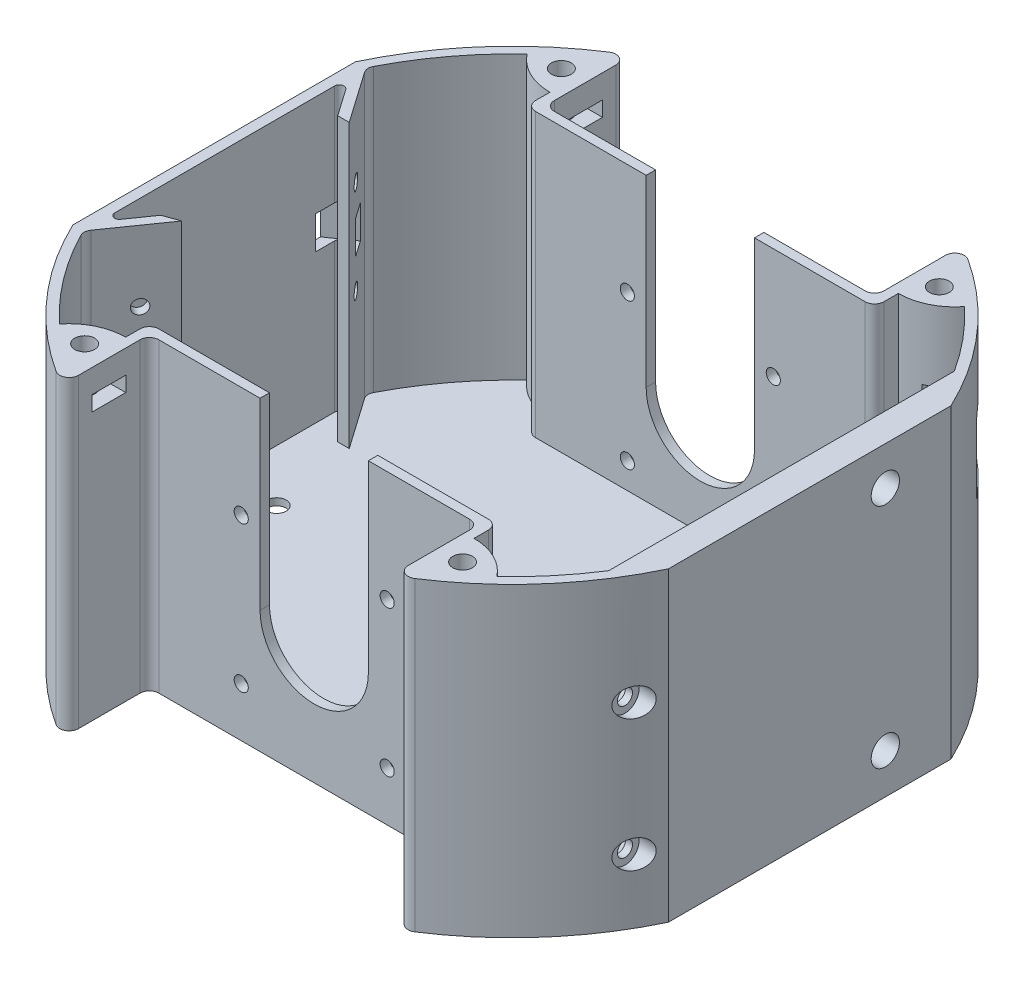
SolidWorks part; units mm, degrees
ref_plane "Plan de face" through (0, 0, 0) normal (0, 0, 1) x (1, 0, 0)
ref_plane "Plan de dessus" through (0, 0, 0) normal (0, 1, 0) x (1, 0, 0)
ref_plane "Plan de droite" through (0, 0, 0) normal (1, 0, 0) x (0, 0, -1)
sketch "Esquisse1" plane through (0, 0, 0) normal (0, 1, 0) x (1, 0, 0)
  line L0 (0, 7.0991) -> (0, -9.5713) construction
  line L1 (-20.3786, 0) -> (23.686, 0) construction
  line L2 (35, 42) -> (-35, 42)
  line L7 (-63.2456, -30) -> (-63.2456, 30)
  line L8 (-35, 42) -> (-35, 60.6218)
  line L9 (-21, 0) -> (-21, 42) construction
  line L12 (-35, -42) -> (-35, -60.6218)
  line L13 (35, -42) -> (-35, -42)
  line L15 (35, -42) -> (35, -60.6218)
  line L16 (63.2456, -30) -> (63.2456, 30)
  line L17 (35, 42) -> (35, 60.6218)
  circle A0 centre (0, 0) radius 70 construction
  arc A1 (-63.2456, 30) -> (-35, 60.6218) centre (0, 0) cw
  arc A2 (-63.2456, -30) -> (-35, -60.6218) centre (0, 0) ccw
  arc A3 (63.2456, -30) -> (35, -60.6218) centre (0, 0) cw
  arc A4 (63.2456, 30) -> (35, 60.6218) centre (0, 0) ccw
  circle A5 centre (-50, 0) radius 2.05
  circle A6 centre (50, 0) radius 2.05
  point P16 (-63.2456, 0)
  point P20 (0, -42)
  point P25 (0, 42)
  dimension "D1" = 140
  dimension "D2" = 42
  dimension "D6" = 4.1
  dimension "D3" = 35
  dimension "D4" = 30
  dimension "D5" = 21
  dimension "D7" = 50
extrude "Boss.-Extru.1" add sketch "Esquisse1" along normal blind 5
sketch "Esquisse3" plane through (0, 5, 0) normal (0, 1, 0) x (1, 0, 0)
  line L0 (-100.0452, 0) -> (128.6597, 0) construction
  line L1 (0, 78.0074) -> (0, -84.0534) construction
  line L2 (-61.0246, -30) -> (-61.0246, 30)
  line L3 (37, 40) -> (-37, 40)
  line L4 (-37, 40) -> (-37, 57.0526)
  line L5 (-63.2456, 30) -> (-61.0246, 30) construction
  line L6 (-37, -40) -> (-37, -57.0526)
  line L7 (37, -40) -> (-37, -40)
  line L8 (-35, 42) -> (-35, 60.6218)
  line L9 (-63.2456, 30) -> (-63.2456, -30)
  line L10 (-35, -60.6218) -> (-35, -42)
  line L11 (-35, -42) -> (35, -42)
  line L12 (35, -42) -> (35, -60.6218)
  line L13 (63.2456, -30) -> (63.2456, 30)
  line L14 (35, 60.6218) -> (35, 42)
  line L15 (35, 42) -> (-35, 42)
  line L16 (-35, 42) -> (-35, 60.6218)
  line L17 (-63.2456, 30) -> (-63.2456, -30)
  line L18 (-35, -60.6218) -> (-35, -42)
  line L19 (-35, -42) -> (35, -42)
  line L20 (35, -42) -> (35, -60.6218)
  line L21 (63.2456, -30) -> (63.2456, 30)
  line L22 (35, 60.6218) -> (35, 42)
  line L23 (35, 42) -> (-35, 42)
  line L24 (37, -40) -> (37, -57.0526)
  line L25 (61.0246, -30) -> (61.0246, 30)
  line L26 (37, 40) -> (37, 57.0526)
  line L27 (-61.0246, 30) -> (-52.4209, 17.7127)
  line L28 (-52.4209, 17.7127) -> (-54.0592, 16.5656)
  line L29 (-54.0592, 16.5656) -> (-61.0246, 26.5131)
  line L30 (-56.7228, 23.8564) -> (-177.37, -60.6218) construction
  line L31 (-52.4209, -17.7127) -> (-54.0592, -16.5656)
  line L32 (-61.0246, -30) -> (-52.4209, -17.7127)
  line L33 (-54.0592, -16.5656) -> (-61.0246, -26.5131)
  line L34 (-56.7228, -23.8564) -> (-177.37, 60.6218) construction
  line L35 (57.2456, 36.7008) -> (57.2456, -36.7008)
  line L36 (51.2707, 60.6218) -> (-111.4939, 60.6218) construction
  line L37 (51.2707, -60.6218) -> (-111.4939, -60.6218) construction
  line L38 (-63.2456, 45.1535) -> (-63.2456, -75.8674) construction
  line L39 (-97.9861, 0) -> (-97.9861, -104.005) construction
  circle A0 centre (0, 0) radius 68 construction
  arc A1 (-37, 57.0526) -> (-61.0246, 30) centre (0, 0) ccw
  arc A2 (-46.4527, 49.6603) -> (-37, 45.0526) centre (-37, 57.0526) ccw
  arc A3 (-37, -57.0526) -> (-61.0246, -30) centre (0, 0) cw
  arc A4 (-35, 60.6218) -> (-63.2456, 30) centre (0, 0) ccw
  arc A5 (-63.2456, -30) -> (-35, -60.6218) centre (0, 0) ccw
  arc A6 (35, -60.6218) -> (63.2456, -30) centre (0, 0) ccw
  arc A7 (63.2456, 30) -> (35, 60.6218) centre (0, 0) ccw
  arc A8 (-35, 60.6218) -> (-63.2456, 30) centre (0, 0) ccw
  arc A9 (-63.2456, -30) -> (-35, -60.6218) centre (0, 0) ccw
  arc A10 (35, -60.6218) -> (63.2456, -30) centre (0, 0) ccw
  arc A11 (63.2456, 30) -> (35, 60.6218) centre (0, 0) ccw
  arc A12 (-46.4527, -49.6603) -> (-37, -45.0526) centre (-37, -57.0526) cw
  arc A13 (37, -57.0526) -> (61.0246, -30) centre (0, 0) ccw
  arc A14 (46.4527, -49.6603) -> (37, -45.0526) centre (37, -57.0526) ccw
  arc A15 (37, 57.0526) -> (61.0246, 30) centre (0, 0) cw
  arc A16 (46.4527, 49.6603) -> (37, 45.0526) centre (37, 57.0526) cw
  circle A17 centre (-134.3793, 0) radius 25 construction
  point P29 (-61.0246, 0)
  point P40 (0, -40)
  point P45 (0, 40)
  point P67 (-149.5717, 0)
  point P68 (0, 0)
  line M27 (-35, 42) -> (-35, 60.6218)
  arc M28 (-35, 60.6218) -> (-63.2456, 30) centre (0, 0) ccw
  line M29 (-63.2456, 30) -> (-63.2456, -30)
  arc M30 (-63.2456, -30) -> (-35, -60.6218) centre (0, 0) ccw
  line M31 (-35, -60.6218) -> (-35, -42)
  line M32 (-35, -42) -> (35, -42)
  line M33 (35, -42) -> (35, -60.6218)
  arc M34 (35, -60.6218) -> (63.2456, -30) centre (0, 0) ccw
  line M35 (63.2456, -30) -> (63.2456, 30)
  arc M36 (63.2456, 30) -> (35, 60.6218) centre (0, 0) ccw
  line M37 (35, 60.6218) -> (35, 42)
  line M38 (35, 42) -> (-35, 42)
  dimension "D2" = 136
  dimension "D3" = 2
  dimension "D5" = 12
  dimension "D13" = 50
  dimension "D4" = 2
  dimension "D6" = 2
  dimension "D7" = 15
  dimension "D8" = 35
  dimension "D9" = 6
  dimension "D11" = 114.1245
  dimension "D12" = 34.7406
  dimension "D14" = 71.1338
  dimension "D1" = 0
extrude "Boss.-Extru.2" add sketch "Esquisse3" along normal blind 60 contours L26 A15 L25 A13 L24 L7 L6 A3 L2 A1 L4 L3 M38 M27 M28 M29 M30 M31 M32 M33 M34 M35 M36 M37 | L29 L28 L27 L2 | A12 A3 L6 | A16 A15 L26 | A13 A14 L24 | L31 L33 L2 L32 | A15 L35 A13 L25 | A1 A2 L4
sketch "Esquisse4" plane through (0, 0, -40) normal (0, 0, 1) x (1, 0, 0)
  line L0 (0, -2.1196) -> (0, 67.1313) construction
  line L1 (0, 104) -> (0, 26) construction
  line L2 (11.5, 104) -> (11.5, 26)
  line L3 (-11.5, 104) -> (-11.5, 26)
  line L4 (-37, 5) -> (37, 5)
  line L5 (37, 5) -> (37, 65)
  line L6 (37, 65) -> (-37, 65)
  line L7 (-37, 65) -> (-37, 5)
  line L8 (-37, 5) -> (37, 5)
  line L9 (37, 5) -> (37, 65)
  line L10 (37, 65) -> (-37, 65)
  line L11 (-37, 65) -> (-37, 5)
  line L12 (-35, 0) -> (35, 0) construction
  line L13 (-35, 0) -> (35, 0)
  line L14 (31.9264, 26) -> (-22.6349, 26) construction
  arc A0 (11.5, 104) -> (-11.5, 104) centre (0, 104) ccw
  arc A1 (-11.5, 26) -> (11.5, 26) centre (0, 26) ccw
  circle A2 centre (-15.5, 41.5) radius 1.5
  circle A3 centre (-15.5, 10.5) radius 1.5
  circle A4 centre (15.5, 10.5) radius 1.5
  circle A5 centre (15.5, 41.5) radius 1.5
  point P9 (0, 65)
  line M14 (37, 65) -> (-37, 65)
  dimension "D3" = 15.5
  dimension "D5" = 3
  dimension "D2" = 23
  dimension "D4" = 15.5
  dimension "D6" = 26
  dimension "D1" = 0
extrude "Enlèv. mat.-Extru.1" cut sketch "Esquisse4" against normal through all both and the other way through all contours L3 A1 L2 M14 | A3 | A2 | A5 | A4
sketch "Esquisse7" plane through (0, 65, 0) normal (0, 1, 0) x (1, 0, 0)
  line L0 (-35, -60.6218) -> (-49.7114, -60.6218) construction
  line L1 (-46.4527, -49.6603) -> (-37, -45.0526) construction
  line L2 (-41.7264, -47.3565) -> (-37, -57.0526) construction
  line L12 (-11.5, 40) -> (-11.5, 42)
  line L13 (-11.5, 42) -> (-35, 42)
  line L14 (-35, 42) -> (-35, 60.6218)
  line L15 (-63.2456, 30) -> (-63.2456, -30)
  line L16 (-35, -60.6218) -> (-35, -42)
  line L17 (-35, -42) -> (-11.5, -42)
  line L24 (-11.5, 40) -> (-11.5, 42)
  line L25 (-11.5, 42) -> (-35, 42)
  line L26 (-35, 42) -> (-35, 60.6218)
  line L27 (-63.2456, 30) -> (-63.2456, -30)
  line L28 (-35, -60.6218) -> (-35, -42)
  line L29 (-35, -42) -> (-11.5, -42)
  line L39 (-11.5, -42) -> (-11.5, -40)
  line L41 (-11.5, -42) -> (-11.5, -40)
  line L43 (-11.5, -40) -> (-37, -40)
  line L45 (-11.5, -40) -> (-37, -40)
  line L47 (-37, -40) -> (-37, -45.0526)
  line L49 (-37, -40) -> (-37, -45.0526)
  line L51 (-61.0246, -26.5131) -> (-61.0246, 26.5131)
  line L53 (-61.0246, -26.5131) -> (-61.0246, 26.5131)
  line L55 (-37, 45.0526) -> (-37, 40)
  line L57 (-37, 45.0526) -> (-37, 40)
  line L59 (-37, 40) -> (-11.5, 40)
  line L61 (-37, 40) -> (-11.5, 40)
  line L63 (-61.0246, -30) -> (-52.4209, -17.7127)
  line L64 (-61.0246, -30) -> (-52.4209, -17.7127)
  line L65 (-52.4209, -17.7127) -> (-54.0592, -16.5656)
  line L66 (-52.4209, -17.7127) -> (-54.0592, -16.5656)
  line L67 (-54.0592, -16.5656) -> (-61.0246, -26.5131)
  line L68 (-54.0592, -16.5656) -> (-61.0246, -26.5131)
  line L69 (-61.0246, 26.5131) -> (-54.0592, 16.5656)
  line L70 (-61.0246, 26.5131) -> (-54.0592, 16.5656)
  line L71 (-54.0592, 16.5656) -> (-52.4209, 17.7127)
  line L72 (-54.0592, 16.5656) -> (-52.4209, 17.7127)
  line L73 (-52.4209, 17.7127) -> (-61.0246, 30)
  line L74 (-52.4209, 17.7127) -> (-61.0246, 30)
  circle A1 centre (-40.1347, -50.6218) radius 2.1
  arc A6 (-35, 60.6218) -> (-63.2456, 30) centre (0, 0) ccw
  arc A7 (-63.2456, -30) -> (-35, -60.6218) centre (0, 0) ccw
  arc A9 (-37, -45.0526) -> (-46.4527, -49.6603) centre (-37, -57.0526) ccw
  arc A10 (-37, -45.0526) -> (-46.4527, -49.6603) centre (-37, -57.0526) ccw
  arc A12 (-35, 60.6218) -> (-63.2456, 30) centre (0, 0) ccw
  arc A13 (-63.2456, -30) -> (-35, -60.6218) centre (0, 0) ccw
  arc A18 (-61.0246, -30) -> (-46.4527, -49.6603) centre (0, 0) ccw
  arc A20 (-61.0246, -30) -> (-46.4527, -49.6603) centre (0, 0) ccw
  arc A22 (-46.4527, 49.6603) -> (-61.0246, 30) centre (0, 0) ccw
  arc A24 (-46.4527, 49.6603) -> (-61.0246, 30) centre (0, 0) ccw
  arc A26 (-46.4527, 49.6603) -> (-37, 45.0526) centre (-37, 57.0526) ccw
  arc A27 (-46.4527, 49.6603) -> (-37, 45.0526) centre (-37, 57.0526) ccw
  dimension "D2" = 4.2
  dimension "D3" = 10
  dimension "D4" = 5.1347
  dimension "D1" = 0
extrude "Enlèv. mat.-Extru.2" cut sketch "Esquisse7" against normal blind 13 contours A1
sketch "Esquisse8" plane through (-35, 0, 0) normal (1, 0, 0) x (0, 0, -1)
  line L1 (-47.0218, 56.8) -> (-54.2218, 56.8)
  line L2 (-47.0218, 56.8) -> (-47.0218, 60)
  line L3 (-47.0218, 60) -> (-54.2218, 60)
  line L4 (-60.6218, 0) -> (-42, 0)
  line L5 (-42, 0) -> (-42, 65)
  line L6 (-42, 65) -> (-60.6218, 65)
  line L7 (-60.6218, 65) -> (-60.6218, 0)
  line L8 (-60.6218, 0) -> (-42, 0)
  line L9 (-42, 0) -> (-42, 65)
  line L10 (-42, 65) -> (-60.6218, 65)
  line L11 (-60.6218, 65) -> (-60.6218, 0)
  line L12 (-54.2218, 56.8) -> (-54.2218, 60)
  line L13 (-47.0218, 56.8) -> (-54.2218, 60) construction
  line L14 (-47.0218, 60) -> (-54.2218, 56.8) construction
  point P2 (-50.6218, 58.4)
  dimension "D2" = 10
  dimension "D3" = 7.2
  dimension "D4" = 3.2
  dimension "D5" = 5
  dimension "D1" = 0
extrude "Enlèv. mat.-Extru.3" cut sketch "Esquisse8" against normal blind 5 contours L2 L1 L12 L3
sketch "Esquisse10" plane through (0, 65, 0) normal (0, 1, 0) x (1, 0, 0)
  line L0 (-40.1347, -50.6218) -> (-35, -50.6218) construction
  line L1 (-35.9778, -50.6218) -> (-38.0562, -47.0218)
  line L2 (-38.0562, -47.0218) -> (-42.2131, -47.0218)
  line L3 (-42.2131, -47.0218) -> (-44.2916, -50.6218)
  line L4 (-44.2916, -50.6218) -> (-42.2131, -54.2218)
  line L5 (-42.2131, -54.2218) -> (-38.0562, -54.2218)
  line L6 (-38.0562, -54.2218) -> (-35.9778, -50.6218)
  line L7 (-35, -60.6218) -> (-35, -42) construction
  circle A0 centre (-40.1347, -50.6218) radius 2.1 construction
  circle A1 centre (-40.1347, -50.6218) radius 2.1
  circle A2 centre (-40.1347, -50.6218) radius 3.6 construction
  dimension "D1" = 7.2
extrude "Enlèv. mat.-Extru.4" cut sketch "Esquisse10" against normal blind 3.2 from offset 5
mirror "Symétrie1" about plane through (0, 0, 0) normal (1, 0, 0) of "Enlèv. mat.-Extru.4", "Enlèv. mat.-Extru.3", "Enlèv. mat.-Extru.2"
mirror "Symétrie2" about plane through (0, 0, 0) normal (0, 0, 1) of "Symétrie1", "Enlèv. mat.-Extru.4", "Enlèv. mat.-Extru.3", "Enlèv. mat.-Extru.2"
fillet "Congé1" radius 2 14 edges at (37, 35, -40) (-35, 32.5, -42) (35, 32.5, -42) (-37, 35, -40) (-35, 32.5, 60.6218) (-35, 32.5, -60.6218) (35, 32.5, -60.6218) (-37, 35, 40) (37, 35, 40) (35, 32.5, 42) (-35, 32.5, 42) (35, 32.5, 60.6218) (-61.0246, 35, -30) (-61.0246, 35, 30)
fillet "Congé2" radius 1 2 edges at (-61.0246, 35, -26.5131) (-61.0246, 35, 26.5131)
sketch "Esquisse13" plane through (0, 0, 0) normal (0, -1, 0) x (1, 0, 0)
  circle A0 centre (-50, 0) radius 2.05 construction
  circle A1 centre (-50, 0) radius 2.05
  circle A2 centre (50, 0) radius 2.05 construction
  circle A3 centre (50, 0) radius 2.05
  circle A4 centre (-50, 0) radius 12.75
  circle A5 centre (50, 0) radius 12.75
  dimension "D1" = 25.5
extrude "Enlèv. mat.-Extru.5" cut sketch "Esquisse13" against normal blind 3.5
sketch "Esquisse14" plane through (-26.8527, 0, -18.8025) normal (0.8192, 0, 0.5736) x (0.5736, 0, -0.8192)
  line L0 (-50.9268, 65) -> (-50.9268, 5) construction
  line L1 (-44.5768, 40) -> (-58.3826, 40) construction
  line L2 (-45.5768, 65) -> (-45.5768, 5) construction
  line L4 (-44.5768, 65) -> (-58.3826, 65)
  line L5 (-58.3826, 65) -> (-58.3826, 5)
  line L6 (-58.3826, 5) -> (-44.5768, 5)
  line L7 (-44.5768, 5) -> (-44.5768, 65)
  line L8 (-44.5768, 65) -> (-58.3826, 65)
  line L9 (-58.3826, 65) -> (-58.3826, 5)
  line L10 (-58.3826, 5) -> (-44.5768, 5)
  line L11 (-44.5768, 5) -> (-44.5768, 65)
  line L15 (-54.7768, 43.5) -> (-50.7768, 43.5)
  line L16 (-54.7768, 43.5) -> (-54.7768, 36.5)
  line L17 (-54.7768, 36.5) -> (-50.7768, 36.5)
  line L18 (-50.7768, 43.5) -> (-50.7768, 36.5)
  line L19 (-54.7768, 43.5) -> (-50.7768, 36.5) construction
  line L20 (-54.7768, 36.5) -> (-50.7768, 43.5) construction
  circle A0 centre (-50.9268, 50) radius 1.5
  circle A2 centre (-50.9268, 30) radius 1.5
  point P12 (-50.9268, 40)
  point P13 (-52.7768, 40)
  dimension "D2" = 20
  dimension "D3" = 3
  dimension "D4" = 4
  dimension "D5" = 7
  dimension "D6" = 1
  dimension "D7" = 35
  dimension "D8" = 9.2
  dimension "D9" = 5.35
  dimension "D1" = 0
extrude "Enlèv. mat.-Extru.6" cut sketch "Esquisse14" against normal blind 5 contours L17 L18 L15 L16 | A0 | A2
sketch "Esquisse16" plane through (-26.8527, 0, -18.8025) normal (0.8192, 0, 0.5736) x (0.5736, 0, -0.8192)
  line L0 (-50.7768, 43.5) -> (-50.7768, 36.5) construction
  line L1 (-54.7768, 43.5) -> (-50.7768, 43.5) construction
  line L2 (-54.7768, 43.5) -> (-54.7768, 36.5) construction
  line L3 (-54.7768, 36.5) -> (-50.7768, 36.5) construction
  line L4 (-50.7768, 43.5) -> (-50.7768, 36.5)
  line L5 (-54.7768, 43.5) -> (-50.7768, 43.5)
  line L6 (-54.7768, 43.5) -> (-54.7768, 36.5)
  line L7 (-54.7768, 36.5) -> (-50.7768, 36.5)
extrude "Enlèv. mat.-Extru.8" cut sketch "Esquisse16" against normal through all
mirror "Symétrie3" about plane through (0, 0, 0) normal (0, 0, 1) of "Enlèv. mat.-Extru.8", "Enlèv. mat.-Extru.6"
sketch "Esquisse18" plane through (57.2456, 0, 0) normal (-1, 0, 0) x (0, 0, 1)
  line L0 (-16.05, 59.34) -> (-16.05, 6) construction
  line L1 (37.29, 6) -> (-31.29, 6) construction
  line L4 (-36.7008, 5) -> (36.7008, 5)
  line L5 (36.7008, 5) -> (36.7008, 65)
  line L6 (36.7008, 65) -> (-36.7008, 65)
  line L7 (-36.7008, 65) -> (-36.7008, 5)
  line L8 (-36.7008, 5) -> (36.7008, 5) construction
  line L9 (36.7008, 5) -> (36.7008, 65) construction
  line L10 (36.7008, 65) -> (-36.7008, 65) construction
  line L11 (-36.7008, 65) -> (-36.7008, 5) construction
  line L14 (37.29, 6) -> (37.29, 59.34) construction
  line L16 (-30, 0) -> (30, 0) construction
  line L17 (37.29, 59.34) -> (-31.29, 59.34) construction
  line L18 (-31.29, 6) -> (-31.29, 59.34) construction
  line L19 (37.29, 6) -> (-31.29, 59.34) construction
  line L20 (37.29, 59.34) -> (-31.29, 6) construction
  line L21 (34.75, 59.34) -> (34.75, 6) construction
  circle A4 centre (-16.05, 56.8) radius 1.6
  circle A5 centre (-16.05, 8.54) radius 1.6
  circle A6 centre (34.75, 41.56) radius 1.6
  circle A7 centre (34.75, 13.62) radius 1.6
  point P4 (3, 32.67)
  dimension "D2" = 3.2
  dimension "D3" = 2.54
  dimension "D4" = 50.8
  dimension "D5" = 53.34
  dimension "D6" = 68.58
  dimension "D7" = 15.24
  dimension "D8" = 66.04
  dimension "D9" = 17.78
  dimension "D10" = 45.72
  dimension "D11" = 6
  dimension "D12" = 3
  dimension "D1" = 0
extrude "Enlèv. mat.-Extru.10" cut sketch "Esquisse18" against normal blind 10 and the other way blind 2.5
sketch "Esquisse19" plane through (63.2456, 0, 0) normal (1, 0, 0) x (0, 0, -1)
  circle A0 centre (16.05, 8.54) radius 1.6 construction
  circle A3 centre (16.05, 56.8) radius 1.6 construction
  circle A4 centre (16.05, 8.54) radius 1.6
  circle A7 centre (16.05, 56.8) radius 1.6
  circle A8 centre (-34.75, 41.56) radius 3
  circle A9 centre (16.05, 56.8) radius 3
  circle A10 centre (-34.75, 13.62) radius 3
  circle A11 centre (16.05, 8.54) radius 3
  circle A12 centre (-34.75, 13.62) radius 1.6 construction
  circle A13 centre (-34.75, 41.56) radius 1.6 construction
  circle A14 centre (-34.75, 13.62) radius 1.6
  circle A15 centre (-34.75, 41.56) radius 1.6
  dimension "D1" = 6
extrude "Enlèv. mat.-Extru.11" cut sketch "Esquisse19" against normal blind 4.5
sketch "Esquisse20" plane through (0, 0, 0) normal (0, -1, 0) x (1, 0, 0)
  line L0 (0, 42) -> (0, -42) construction
  line L1 (-33, 42) -> (33, 42) construction
  line L2 (33, -42) -> (-33, -42) construction
  text T0 "Serge V1" font "Century Gothic" height in points 26
extrude "Enlèv. mat.-Extru.12" cut sketch "Esquisse20" against normal blind 0.2
chamfer "Chanfrein1" distance 2 angle 55 2 edges at (-54.0592, 35, -16.5656) (-54.0592, 35, 16.5656)
sketch "Esquisse21" plane through (0, 0, 0) normal (0, 0, 1) x (1, 0, 0)
  line L0 (41.2456, 65) -> (41.2456, 35)
  line L1 (41.2456, 35) -> (53.2456, 35)
  line L2 (53.2456, 35) -> (53.2456, 65)
  line L3 (41.2456, 50) -> (53.2456, 50)
  line L4 (63.2456, 65) -> (38.0882, 65)
  line L5 (38.0882, 65) -> (38.0882, 0)
  line L6 (38.0882, 0) -> (63.2456, 0)
  line L7 (63.2456, 0) -> (63.2456, 65)
  line L8 (63.2456, 65) -> (38.0882, 65)
  line L9 (38.0882, 65) -> (38.0882, 0)
  line L10 (38.0882, 0) -> (63.2456, 0)
  line L11 (63.2456, 0) -> (63.2456, 65)
  dimension "D2" = 10
  dimension "D3" = 12
  dimension "D4" = 30
  dimension "D5" = 15
  dimension "D1" = 0
extrude "Enlèv. mat.-Extru.13" cut sketch "Esquisse21" against normal through all contours L3 L0 L1 L2 | L8 L9 L10 L11
